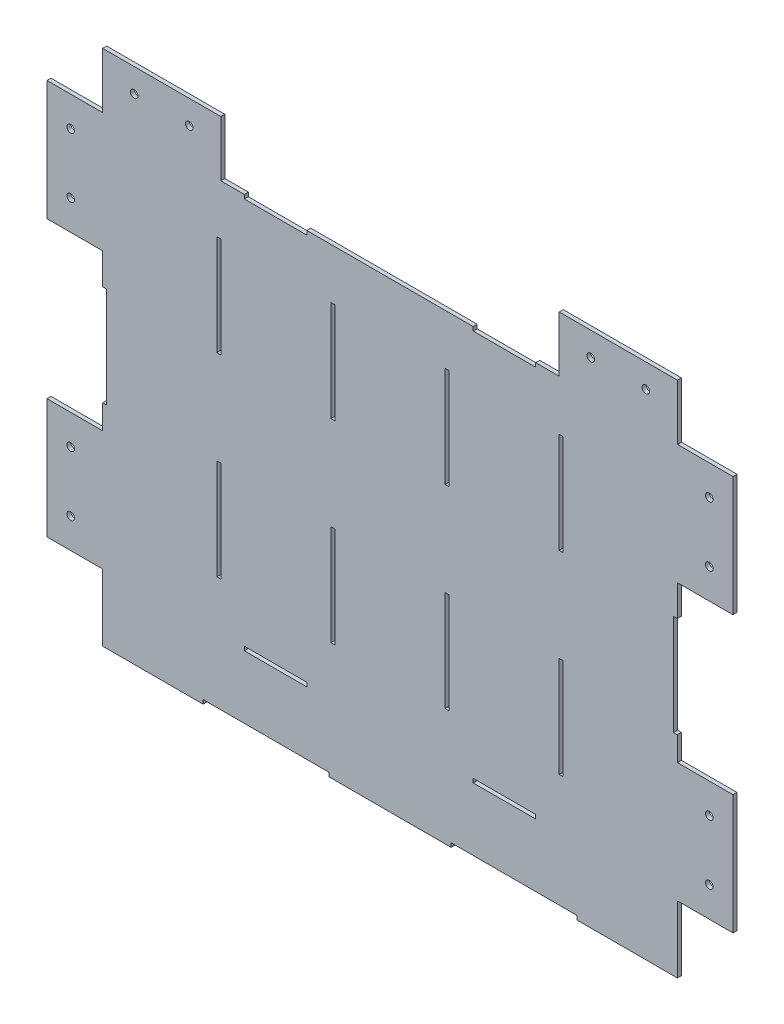
SolidWorks part; units mm, degrees
material "6061-T6 (SS)"
ref_plane "X-Y Datum" through (0, 0, 0) normal (0, 0, 1) x (1, 0, 0)
ref_plane "X-Z Datum" through (0, 0, 0) normal (0, 1, 0) x (1, 0, 0)
ref_plane "Y-Z Datum" through (0, 0, 0) normal (1, 0, 0) x (0, 0, -1)
sketch "Sketch1" plane through (0, 0, 0) normal (0, 0, 1) x (1, 0, 0)
  line L0 (-228.6115, 0) -> (228.6115, 0) construction
  line L1 (-228.6115, -157.216) -> (228.6115, -157.216)
  line L2 (-228.6115, -157.216) -> (-228.6115, 157.216)
  line L3 (-228.6115, 157.216) -> (228.6115, 157.216)
  line L4 (228.6115, -157.216) -> (228.6115, 157.216)
  line L5 (-228.6115, -157.216) -> (228.6115, 157.216) construction
  line L6 (-228.6115, 157.216) -> (228.6115, -157.216) construction
  line L8 (-228.6115, 0) -> (-134.6215, 0) construction
  line L9 (-225.4325, -154.041) -> (-225.4325, 154.041)
  line L10 (-224.4165, -153.025) -> (-138.8165, -153.025) construction
  line L15 (-224.4165, -153.025) -> (-224.4165, 153.025) construction
  line L16 (-224.4165, 153.025) -> (-138.8165, 153.025) construction
  line L17 (-138.8165, -153.025) -> (-138.8165, 153.025) construction
  line L18 (-224.4165, -153.025) -> (-138.8165, 153.025) construction
  line L19 (-224.4165, 153.025) -> (-138.8165, -153.025) construction
  line L20 (-225.4325, 154.041) -> (-137.8005, 154.041)
  line L21 (-137.8005, -154.041) -> (-137.8005, 154.041)
  line L22 (-225.4325, -154.041) -> (-137.8005, -154.041)
  line L26 (-134.6255, 154.041) -> (-46.9935, 154.041)
  line L27 (-133.6095, -153.025) -> (-48.0095, -153.025) construction
  line L28 (-133.6095, -153.025) -> (-133.6095, 153.025) construction
  line L29 (-133.6095, 153.025) -> (-48.0095, 153.025) construction
  line L30 (-48.0095, -153.025) -> (-48.0095, 153.025) construction
  line L31 (-133.6095, -153.025) -> (-48.0095, 153.025) construction
  line L32 (-133.6095, 153.025) -> (-48.0095, -153.025) construction
  line L33 (-46.9935, -154.041) -> (-46.9935, 154.041)
  line L34 (-134.6255, -154.041) -> (-46.9935, -154.041)
  line L35 (-134.6255, -154.041) -> (-134.6255, 154.041)
  line L36 (42.7975, -153.025) -> (42.7975, 153.025) construction
  line L37 (43.8135, -154.041) -> (43.8135, 154.041)
  line L38 (-42.8025, -153.025) -> (42.7975, 153.025) construction
  line L39 (-42.8025, 153.025) -> (42.7975, -153.025) construction
  line L40 (-42.8025, -153.025) -> (-42.8025, 153.025) construction
  line L41 (-43.8185, -154.041) -> (-43.8185, 154.041)
  line L42 (-42.8025, 153.025) -> (42.7975, 153.025) construction
  line L43 (-43.8185, 154.041) -> (43.8135, 154.041)
  line L44 (-42.8025, -153.025) -> (42.7975, -153.025) construction
  line L45 (-43.8185, -154.041) -> (43.8135, -154.041)
  line L46 (133.6045, -153.025) -> (133.6045, 153.025) construction
  line L47 (134.6205, -154.041) -> (134.6205, 154.041)
  line L48 (48.0045, -153.025) -> (133.6045, 153.025) construction
  line L49 (48.0045, 153.025) -> (133.6045, -153.025) construction
  line L50 (48.0045, -153.025) -> (48.0045, 153.025) construction
  line L51 (46.9885, -154.041) -> (46.9885, 154.041)
  line L52 (48.0045, 153.025) -> (133.6045, 153.025) construction
  line L53 (46.9885, 154.041) -> (134.6205, 154.041)
  line L54 (48.0045, -153.025) -> (133.6045, -153.025) construction
  line L55 (46.9885, -154.041) -> (134.6205, -154.041)
  line L56 (224.4115, -153.025) -> (224.4115, 153.025) construction
  line L57 (225.4275, -154.041) -> (225.4275, 154.041)
  line L58 (138.8115, -153.025) -> (224.4115, 153.025) construction
  line L59 (138.8115, 153.025) -> (224.4115, -153.025) construction
  line L60 (138.8115, -153.025) -> (138.8115, 153.025) construction
  line L61 (137.7955, -154.041) -> (137.7955, 154.041)
  line L62 (138.8115, 153.025) -> (224.4115, 153.025) construction
  line L63 (137.7955, 154.041) -> (225.4275, 154.041)
  line L64 (138.8115, -153.025) -> (224.4115, -153.025) construction
  line L65 (137.7955, -154.041) -> (225.4275, -154.041)
  line L67 (-228.6115, -157.216) -> (225.4365, -157.216)
  line L71 (-228.6115, -157.216) -> (228.6115, -157.216)
  line L74 (-225.4365, -157.216) -> (225.4365, -157.216)
  line L75 (-225.4365, -157.216) -> (-225.4365, -208.106)
  line L76 (-225.4365, -208.106) -> (225.4365, -208.106)
  line L77 (225.4365, -157.216) -> (225.4365, -208.106)
  line L79 (-228.6115, -157.216) -> (228.6115, -157.216)
  line L80 (-228.6115, -157.216) -> (-228.6115, -210.392)
  line L81 (-228.6115, -210.392) -> (228.6115, -210.392)
  line L82 (228.6115, -157.216) -> (228.6115, -210.392)
  point P0 (0, 0)
  point P10 (-181.6165, 0)
  point P22 (-90.8095, 0)
  dimension "D1" = 314.432
  dimension "D2" = 457.223
  dimension "D4" = 1.016
  dimension "D5" = 3.179
  dimension "D6" = 3.175
  dimension "D7" = 1.016
  dimension "D8" = 90.807
  dimension "D9" = 3.175
  dimension "D11" = 3.175
  dimension "D12" = 50.89
  dimension "D13" = 2.286
  dimension "D14" = 3.175
  dimension "D15" = 3.175
  dimension "D10" = 4
extrude "Boss-Extrude2" add sketch "Sketch1" along normal blind 3.175 contours L61 L65 L57 L63 | L51 L55 L47 L53 | L41 L45 L37 L43 | L35 L34 L33 L26 | L9 L22 L21 L20 | L1 L71 L4 L3 L2 L65 L61 L63 L57 L55 L51 L53 L47 L45 L41 L43 L37 L22 L9 L20 L21 L34 L35 L26 L33 | L77 L71 L75 L76 | L82 L1 L77 L76 L75 L80 L81 region at (-228.0566, 0, 0) region at (-227.024, -161.819, 0) region at (0, -182.661, 0) region at (-181.6165, 0, 0) region at (-90.8095, 0, 0) region at (-0.0025, 0, 0) region at (90.8045, 0, 0) region at (181.6115, 0, 0)
sketch "Sketch4" plane through (0, 0, 3.175) normal (0, 0, 1) x (1, 0, 0)
  line L0 (-136.213, 117.216) -> (-136.213, 157.216) construction
  line L1 (-228.6115, 157.216) -> (228.6115, 157.216) construction
  line L2 (-228.6115, 157.216) -> (228.6115, 157.216) construction
  line L5 (-134.6255, -154.041) -> (-134.6255, 154.041) construction
  line L6 (-137.8005, 37.216) -> (-134.6255, 37.216)
  line L7 (-137.8005, 37.216) -> (-137.8005, 117.216)
  line L8 (-137.8005, 117.216) -> (-134.6255, 117.216)
  line L9 (-134.6255, 37.216) -> (-134.6255, 117.216)
  line L10 (-137.8005, 37.216) -> (-134.6255, 117.216) construction
  line L11 (-137.8005, 117.216) -> (-134.6255, 37.216) construction
  line L13 (-45.406, 153.025) -> (-45.406, -157.216) construction
  line L14 (-228.6115, -157.216) -> (228.6115, -157.216) construction
  dimension "D1" = 40
  dimension "D2" = 3.175
  dimension "D3" = 80
  dimension "D4" = 90.807
extrude "Cut-Extrude1" cut sketch "Sketch4" against normal blind 3.175 contours L6 L9 L8 L7 region at (-136.213, 77.216, 3.175)
mirror "Mirror1" about plane through (0, 0, 0) normal (0, 1, 0) of "Cut-Extrude1"
pattern_linear "LPattern1" count 4 spacing 90.807 along (1, 0, 0) of "Mirror1"
sketch "Sketch5" plane through (0, 0, 3.175) normal (0, 0, 1) x (1, 0, 0)
  line L0 (-225.4365, -157.216) -> (-228.6115, -157.216)
  line L1 (-225.4325, -154.041) -> (-228.6115, -154.041)
  line L2 (-228.6115, -157.216) -> (-228.6115, 157.216) construction
  line L3 (-228.6115, -154.041) -> (-228.6115, -157.216)
  line L4 (-228.6115, -155.6285) -> (-194.996, -155.6285)
  line L5 (-194.996, -155.6285) -> (-91.0201, -155.6285) construction
  line L6 (-225.4325, -154.041) -> (-137.8005, -154.041) construction
  line L7 (-115.8495, -157.216) -> (-66.1907, -157.216)
  line L8 (-115.8495, -157.216) -> (-115.8495, -154.041)
  line L9 (-115.8495, -154.041) -> (-66.1907, -154.041)
  line L10 (-66.1907, -157.216) -> (-66.1907, -154.041)
  line L11 (-115.8495, -157.216) -> (-66.1907, -154.041) construction
  line L12 (-115.8495, -154.041) -> (-66.1907, -157.216) construction
  dimension "D1" = 112.762
  dimension "D2" = 49.6588
extrude "Cut-Extrude2" cut sketch "Sketch5" against normal blind 3.175 contours L7 L10 L9 L8 region at (-91.0201, -155.6285, 3.175)
mirror "Mirror2" about plane through (0, 0, 0) normal (1, 0, 0) of "Cut-Extrude2"
mirror "Mirror3" about plane through (0, 0, 0) normal (0, 1, 0) of "Mirror2"
sketch "Sketch6" plane through (0, 0, 3.175) normal (0, 0, 1) x (1, 0, 0)
  line L0 (-228.6115, -210.392) -> (-228.6115, 157.216) construction
  line L3 (-228.6115, 157.216) -> (-115.8495, 157.216) construction
  line L5 (-225.4365, 157.216) -> (-228.6115, 157.216)
  line L6 (-227.024, 157.216) -> (-227.024, 37.216) construction
  line L7 (-227.024, 37.216) -> (-227.024, -42.784) construction
  line L9 (-225.4365, -42.784) -> (-228.6115, -42.784)
  line L10 (-225.4365, -42.784) -> (-225.4365, 37.216)
  line L11 (-225.4365, 37.216) -> (-228.6115, 37.216)
  line L12 (-228.6115, -42.784) -> (-228.6115, 37.216)
  line L13 (-225.4365, -42.784) -> (-228.6115, 37.216) construction
  line L14 (-225.4365, 37.216) -> (-228.6115, -42.784) construction
  point P11 (-227.024, -2.784)
  dimension "D1" = 3.175
  dimension "D2" = 120
  dimension "D3" = 80
extrude "Cut-Extrude3" cut sketch "Sketch6" against normal through all contours L12 L9 L10 L11 region at (-227.024, -2.784, 3.175)
mirror "Mirror5" about plane through (0, 0, 0) normal (1, 0, 0) of "Cut-Extrude3"
sketch "Sketch7" plane through (0, 0, 3.175) normal (0, 0, 1) x (1, 0, 0)
  line L1 (-228.6115, -210.392) -> (-228.6115, -42.784) construction
  line L5 (-148.6115, -210.392) -> (-48.6115, -210.392)
  line L6 (-148.6115, -210.392) -> (-148.6115, -207.217)
  line L7 (-148.6115, -207.217) -> (-48.6115, -207.217)
  line L8 (-48.6115, -210.392) -> (-48.6115, -207.217)
  line L9 (-148.6115, -210.392) -> (-48.6115, -207.217) construction
  line L10 (-148.6115, -207.217) -> (-48.6115, -210.392) construction
  point P7 (-98.6115, -208.8045)
  dimension "D1" = 80
  dimension "D2" = 100
  dimension "D3" = 3.175
extrude "Cut-Extrude4" cut sketch "Sketch7" against normal blind 3.175 contours L5 L8 L7 L6 region at (-98.6115, -208.8045, 3.175)
mirror "Mirror6" about plane through (0, 0, 0) normal (1, 0, 0) of "Cut-Extrude4"
sketch "Sketch8" plane through (0, 0, 0) normal (0, 0, -1) x (-1, 0, 0)
  line L0 (-228.6115, -210.392) -> (-228.6115, -42.784) construction
  line L1 (-228.6115, 157.216) -> (-279.4115, 157.216)
  line L2 (-228.6115, 157.216) -> (-228.6115, 61.966)
  line L3 (-228.6115, 61.966) -> (-279.4115, 61.966)
  line L4 (-279.4115, 157.216) -> (-279.4115, 61.966)
  line L5 (-228.6115, -157.2452) -> (-279.4115, -157.2452)
  line L6 (-228.6115, -157.2452) -> (-228.6115, -61.9952)
  line L7 (-228.6115, -61.9952) -> (-279.4115, -61.9952)
  line L8 (-279.4115, -157.2452) -> (-279.4115, -61.9952)
  line L9 (-254.0115, 157.216) -> (-254.0115, 61.966) construction
  line L10 (-254.0115, -85.8077) -> (-254.0115, -133.4327) construction
  line L11 (-279.4115, 109.591) -> (-228.6115, 109.591) construction
  line L12 (-254.0115, 157.216) -> (-254.0115, 109.591) construction
  line L13 (-272.8865, 157.216) -> (-272.8865, 61.966)
  line L14 (-148.6115, -210.392) -> (-228.6115, -210.392) construction
  line L15 (-228.6115, -109.6202) -> (-279.4115, -109.6202) construction
  line L16 (-181.6215, 201.491) -> (-181.6215, 157.216) construction
  line L17 (-228.6115, 157.216) -> (-134.6315, 157.216)
  line L18 (-228.6115, 157.216) -> (-228.6115, 201.491)
  line L19 (-228.6115, 201.491) -> (-134.6315, 201.491)
  line L20 (-134.6315, 157.216) -> (-134.6315, 201.491)
  line L21 (-228.6115, 179.3535) -> (-134.6315, 179.3535) construction
  line L22 (-159.714, 185.616) -> (-134.6315, 185.616) construction
  line L23 (-272.8865, -61.9952) -> (-272.8865, -157.2452)
  circle A1 centre (-254.0115, 133.4035) radius 3
  circle A2 centre (-254.0115, 85.7785) radius 3
  circle A3 centre (-254.0115, -85.8077) radius 3
  circle A4 centre (-254.0115, -133.4327) radius 3
  circle A5 centre (-203.529, 182.616) radius 3
  circle A6 centre (-159.714, 182.616) radius 3
  point P13 (-254.0115, -109.6202)
  point P44 (-257.0115, 133.4035)
  point P45 (-254.0115, -136.4327)
  point P46 (-254.0115, -157.2452)
  dimension "D1" = 95.25
  dimension "D2" = 15.875
  dimension "D4" = 47.625
  dimension "D8" = 53.1468
  dimension "D9" = 6
  dimension "D13" = 43.815
  dimension "D14" = 6
  dimension "D3" = 25.4
  dimension "D10" = 25.4
  dimension "D11" = 15.875
  dimension "D12" = 93.98
extrude "Boss-Extrude3" add sketch "Sketch8" against normal blind 3.175 contours L1 L4 L3 L2 A1 A2 | L17 L20 L19 L18 A5 A6 | L8 L5 L6 L7 A3 A4 region at (250.7047, 109.591, 0) region at (181.6215, 179.3086, 0) region at (250.7047, -109.6202, 0)
mirror "Mirror7" about plane through (0, 0, 0) normal (1, 0, 0) of "Boss-Extrude3"
